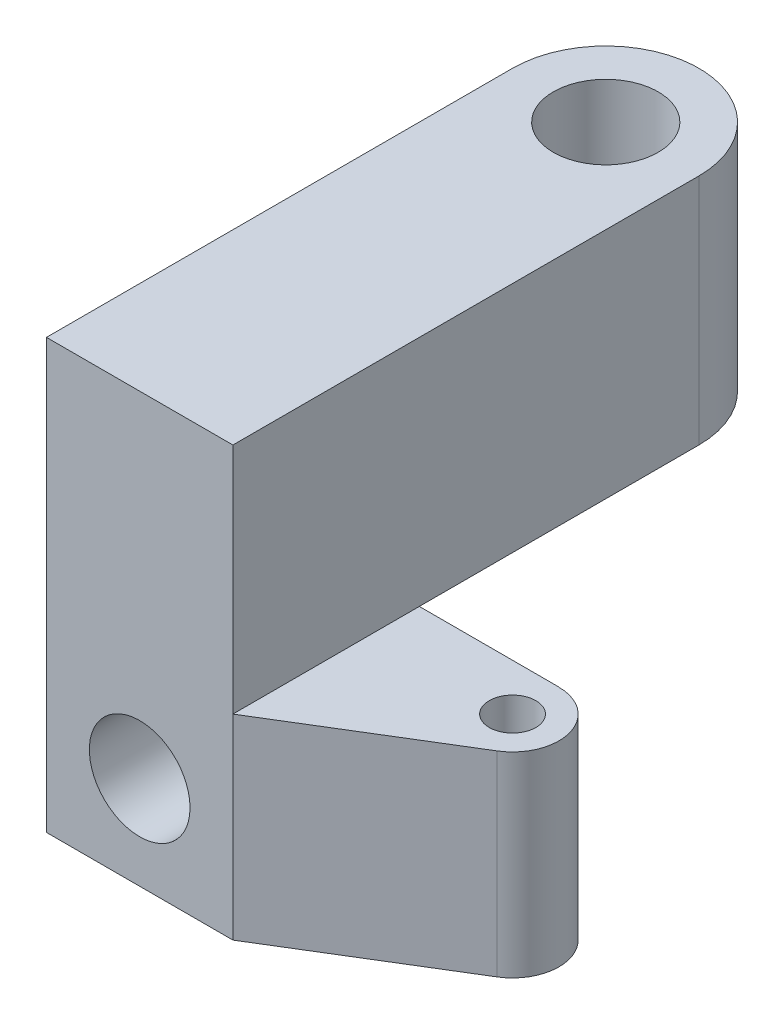
SolidWorks part; units mm, degrees
ref_plane "Front Plane" through (0, 0, 0) normal (0, 0, 1) x (1, 0, 0)
ref_plane "Top Plane" through (0, 0, 0) normal (0, 1, 0) x (1, 0, 0)
ref_plane "Right Plane" through (0, 0, 0) normal (1, 0, 0) x (0, 0, -1)
sketch "Sketch6" plane through (0, 0, 0) normal (0, 1, 0) x (1, 0, 0)
  line L0 (0, 16.9333) -> (0, 10.5833) construction
  line L1 (-6.35, -21.1667) -> (6.35, -21.1667)
  line L2 (-6.35, -21.1667) -> (-6.35, 10.5833)
  line L4 (6.35, -21.1667) -> (6.35, 10.5833)
  line L5 (-6.35, -21.1667) -> (4.5146, 15.0488) construction
  line L6 (-4.5146, 15.0488) -> (6.35, -21.1667) construction
  arc A0 (6.35, 10.5833) -> (-6.35, 10.5833) centre (0, 10.5833) ccw
  circle A1 centre (0, 10.5833) radius 3.175
  point P0 (0, 0)
  dimension "D1" = 31.75
  dimension "D2" = 6.35
extrude "Boss-Extrude4" add sketch "Sketch6" along normal blind 25.4 contours A0 L2 L1 L4
sketch "Sketch7" plane through (0, 0, 0) normal (0, -1, 0) x (1, 0, 0)
  circle A0 centre (0, -10.5833) radius 3.175
extrude "Cut-Extrude1" cut sketch "Sketch7" against normal up to next
ref_plane "Plane2" through (0, 0, -16.9333) normal (0, 0, 1) x (1, 0, 0)
sketch "Sketch9" plane through (0, 0, -16.9333) normal (0, 0, 1) x (1, 0, 0)
  line L1 (7.1567, 0) -> (-6.9125, 0)
  line L2 (7.1567, 0) -> (7.1567, 9.525)
  line L3 (7.1567, 9.525) -> (-6.9125, 9.525)
  line L4 (-6.9125, 0) -> (-6.9125, 9.525)
extrude "Cut-Extrude2" cut sketch "Sketch9" along normal blind 25.4
sketch "Sketch10" plane through (6.35, 0, 0) normal (1, 0, 0) x (0, 0, -1)
  line L1 (-21.1667, 0) -> (-8.4667, 0)
  line L2 (-21.1667, 0) -> (-21.1667, 9.525)
  line L3 (-21.1667, 9.525) -> (-8.4667, 9.525)
  line L4 (-8.4667, 0) -> (-8.4667, 9.525)
extrude "Boss-Extrude5" add sketch "Sketch10" along normal blind 12.7
sketch "Sketch11" plane through (0, 9.525, 0) normal (0, 1, 0) x (1, 0, 0)
  line L0 (19.05, -8.4667) -> (19.05, -11.6417) construction
  line L1 (19.05, -8.4667) -> (19.05, -21.1667) construction
  line L2 (19.05, -11.6417) -> (15.875, -11.6417) construction
  line L4 (15.875, -8.4667) -> (6.35, -8.4667)
  line L5 (6.35, -8.4667) -> (19.05, -8.4667)
  line L6 (19.05, -8.4667) -> (19.05, -21.1667)
  line L7 (19.05, -21.1667) -> (6.35, -21.1667)
  line L8 (6.35, -21.1667) -> (17.5276, -14.3526)
  arc A0 (17.5276, -14.3526) -> (15.875, -8.4667) centre (15.875, -11.6417) ccw
  circle A1 centre (15.875, -11.6417) radius 1.5875
  line M4 (6.35, -21.1667) -> (19.05, -21.1667)
  line M5 (19.05, -21.1667) -> (19.05, -8.4667)
  line M6 (19.05, -8.4667) -> (6.35, -8.4667)
extrude "Cut-Extrude3" cut sketch "Sketch11" against normal blind 12.7 contours A0 L6 M6 | A0 M4 M5 | A1 region at (14.8563, 9.525, 18.5319) region at (18.3408, 9.525, 9.1759) region at (15.875, 9.525, 11.6417)
sketch "Sketch13" plane through (0, 9.525, 0) normal (0, 1, 0) x (1, 0, 0)
  line L1 (6.35, -8.4667) -> (19.05, -8.4667)
  line L2 (6.35, -8.4667) -> (6.35, -21.1667)
  line L3 (6.35, -21.1667) -> (19.05, -21.1667)
  line L4 (19.05, -8.4667) -> (19.05, -21.1667)
  dimension "D1" = 12.7
  dimension "D2" = 12.7
extrude "Boss-Extrude6" add sketch "Sketch13" against normal blind 9.525
sketch "Sketch14" plane through (0, 9.525, 0) normal (0, -1, 0) x (1, 0, 0)
  circle A0 centre (0, -10.5833) radius 3.175
extrude "Boss-Extrude7" add sketch "Sketch14" against normal blind 15.875
sketch "Sketch15" plane through (0, 9.525, 0) normal (0, 1, 0) x (1, 0, 0)
  line L0 (19.05, -8.4667) -> (15.875, -8.4667) construction
  line L1 (19.05, -8.4667) -> (6.35, -8.4667) construction
  line L2 (15.875, -8.4667) -> (15.875, -11.6417) construction
  line L3 (19.05, -8.4667) -> (15.875, -8.4667)
  line L4 (15.875, -8.4667) -> (15.875, -8.4794)
  line L5 (19.05, -8.4667) -> (19.05, -21.1667)
  line L6 (19.05, -21.1667) -> (6.35, -21.1667)
  line L7 (6.35, -21.1667) -> (17.5237, -14.3402)
  circle A0 centre (15.875, -11.6417) radius 1.5875
  arc A1 (17.5237, -14.3402) -> (15.875, -8.4794) centre (15.875, -11.6417) ccw
extrude "Cut-Extrude5" cut sketch "Sketch15" against normal blind 12.7
sketch "Sketch16" plane through (0, 25.4, 0) normal (0, 1, 0) x (1, 0, 0)
  circle A0 centre (0, 10.5833) radius 3.5719
  dimension "D1" = 7.1437
extrude "Cut-Extrude6" cut sketch "Sketch16" against normal up to vertex (15.875 mm away) up to point (-6.35, 9.525, -10.5833)
sketch "Sketch17" plane through (0, 0, 0) normal (0, -1, 0) x (1, 0, 0)
  line L0 (6.35, 21.1667) -> (-6.35, 21.1667)
  line L1 (-6.35, 21.1667) -> (-6.35, 8.4667)
  line L2 (-6.35, 8.4667) -> (15.875, 8.4667)
  line L3 (6.35, 21.1667) -> (17.5237, 14.3402)
  arc A0 (15.875, 8.4667) -> (17.2816, 14.4881) centre (15.875, 11.6417) ccw
  circle A1 centre (15.875, 11.6417) radius 1.5875
  circle M1 centre (15.875, 11.6417) radius 1.5875
  arc M2 (15.875, 8.4794) -> (17.5237, 14.3402) centre (15.875, 11.6417) ccw
  line M3 (17.5237, 14.3402) -> (6.35, 21.1667)
  line M4 (6.35, 21.1667) -> (-6.35, 21.1667)
  line M5 (-6.35, 21.1667) -> (-6.35, 8.4667)
  line M6 (-6.35, 8.4667) -> (15.875, 8.4667)
  line M7 (15.875, 8.4667) -> (15.875, 8.4794)
extrude "Boss-Extrude8" add sketch "Sketch17" along normal blind 3.81 contours L3 M7 M2 M3 M4 M5 M6 M1 region at (4.3486, 0, 14.2572)
sketch "Sketch18" plane through (0, 0, 21.1667) normal (0, 0, 1) x (1, 0, 0)
  circle A0 centre (0, 2.54) radius 3.429
extrude "Cut-Extrude7" cut sketch "Sketch18" against normal blind 12.7
